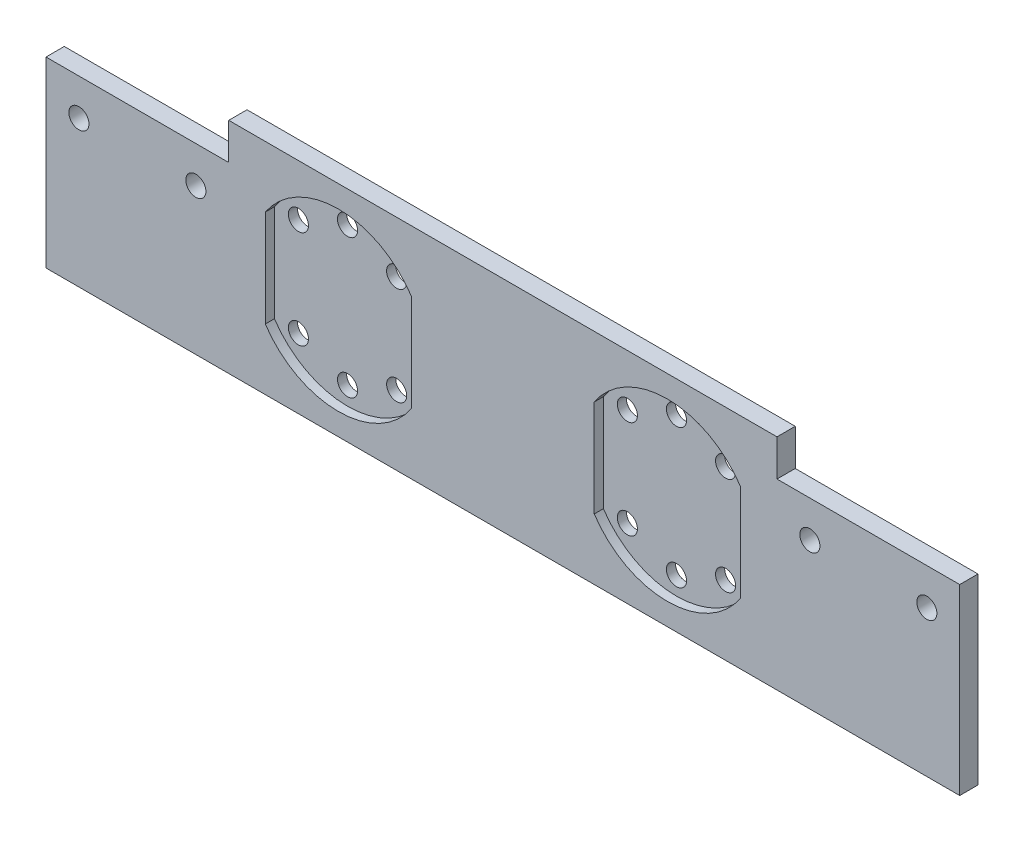
SolidWorks part; units mm, degrees
ref_plane "정면" through (0, 0, 0) normal (0, 0, 1) x (1, 0, 0)
ref_plane "윗면" through (0, 0, 0) normal (0, 1, 0) x (1, 0, 0)
ref_plane "우측면" through (0, 0, 0) normal (1, 0, 0) x (0, 0, -1)
sketch "스케치1" plane through (0, 0, 0) normal (0, 0, 1) x (1, 0, 0)
  line L1 (-145, 25) -> (145, 25)
  line L2 (-145, 25) -> (-145, -25)
  line L3 (-145, -25) -> (145, -25)
  line L4 (145, 25) -> (145, -25)
  line L5 (-145, 25) -> (145, -25) construction
  line L6 (-145, -25) -> (145, 25) construction
  point P0 (0, 0)
  dimension "D1" = 290
  dimension "D2" = 50
extrude "보스-돌출1" add sketch "스케치1" along normal blind 5
sketch "스케치3" plane through (0, 0, 5) normal (0, 0, 1) x (1, 0, 0)
  line L0 (-145, -25) -> (145, -25) construction
  line L1 (-145, 25) -> (-125, 25)
  line L2 (-145, 25) -> (-145, -25)
  line L3 (-145, -25) -> (-125, -25)
  line L4 (-125, 25) -> (-125, -25)
  dimension "D1" = 20
extrude "컷-돌출1" cut sketch "스케치3" against normal blind 10
mirror "대칭 복사1" about plane through (0, 0, 0) normal (1, 0, 0) of "컷-돌출1"
sketch "스케치4" plane through (0, 25, 0) normal (0, 1, 0) x (1, 0, 0)
  line L0 (125, 0) -> (-125, 0) construction
  line L1 (75, 0) -> (-75, 0)
  line L2 (75, 0) -> (75, -5)
  line L3 (75, -5) -> (-75, -5)
  line L4 (-75, 0) -> (-75, -5)
  line L5 (125, -5) -> (-125, -5) construction
  line L6 (-125, 0) -> (-125, -5) construction
  line L7 (125, 0) -> (125, -5) construction
  dimension "D1" = 50
  dimension "D2" = 50
extrude "보스-돌출2" add sketch "스케치4" along normal blind 10
sketch "스케치2" plane through (0, 0, 5) normal (0, 0, 1) x (1, 0, 0)
  line L0 (65, 18.26) -> (65, -8.27)
  line L1 (25, 18.263) -> (25, -8.273)
  line L2 (125, -25) -> (125, 25) construction
  line L3 (-125, -25) -> (125, -25) construction
  line L4 (9.7684, 4.995) -> (97.0125, 4.995) construction
  line L5 (44.999, 41.2348) -> (44.999, -42.4598) construction
  line L6 (0, -2.75) -> (0, 2.75) construction
  line L7 (-25, 18.263) -> (-25, -8.273)
  line L8 (-65, 18.26) -> (-65, -8.27)
  arc A0 (25, 18.263) -> (65, 18.26) centre (44.999, 4.995) cw
  arc A1 (25, -8.273) -> (65, -8.27) centre (44.999, 4.995) ccw
  circle A2 centre (58.44, -8.437) radius 2.75
  circle A3 centre (31.558, -8.437) radius 2.75
  circle A4 centre (44.999, -14) radius 2.75
  circle A5 centre (58.44, 18.427) radius 2.75
  circle A6 centre (44.999, 23.99) radius 2.75
  circle A7 centre (31.558, 18.427) radius 2.75
  circle A8 centre (-31.558, 18.427) radius 2.75
  circle A9 centre (-44.999, 23.99) radius 2.75
  circle A10 centre (-58.44, 18.427) radius 2.75
  circle A11 centre (-44.999, -14) radius 2.75
  circle A12 centre (-31.558, -8.437) radius 2.75
  circle A13 centre (-58.44, -8.437) radius 2.75
  arc A14 (-25, -8.273) -> (-65, -8.27) centre (-44.999, 4.995) cw
  arc A15 (-25, 18.263) -> (-65, 18.26) centre (-44.999, 4.995) ccw
  point P44 (0, 0)
  dimension "D4" = 24
  dimension "D5" = 24
  dimension "D7" = 5.5
  dimension "D11" = 5.5
  dimension "D1" = 60
  dimension "D2" = 100
  dimension "D3" = 26.53
  dimension "D6" = 16.73
  dimension "D8" = 16.563
  dimension "D9" = 6.56
  dimension "D10" = 11
extrude "컷-돌출2" cut sketch "스케치2" against normal blind 2.5
extrude "컷-돌출3" cut sketch "스케치2<2>" against normal through all contours A10 | A9 | A8 | A13 | A11 | A12 | A2 | A5 | A6 | A7 | A3 | A4 region at (58.44, -8.437, 5) region at (58.44, 18.427, 5) region at (44.999, 23.99, 5) region at (31.558, 18.427, 5) region at (-31.558, 18.427, 5) region at (-44.999, 23.99, 5) region at (-58.44, 18.427, 5) region at (-44.999, -14, 5) region at (-31.558, -8.437, 5) region at (-58.44, -8.437, 5)
sketch "스케치2<2>" plane through (0, 0, 5) normal (0, 0, 1) x (1, 0, 0) same geometry as "스케치2"
sketch "스케치5" plane through (0, 0, 5) normal (0, 0, 1) x (1, 0, 0)
  line L0 (-75, 25) -> (-125, 25) construction
  line L1 (-125, -25) -> (-125, 25) construction
  line L2 (0, -2.75) -> (0, 2.75) construction
  circle A0 centre (-84, 15) radius 2.75
  circle A1 centre (-116, 15) radius 2.75
  circle A2 centre (116, 15) radius 2.75
  circle A3 centre (84, 15) radius 2.75
  dimension "D3" = 5.5
  dimension "D4" = 5.5
  dimension "D5" = 9
  dimension "D1" = 10
  dimension "D2" = 10
  dimension "D6" = 41
extrude "컷-돌출4" cut sketch "스케치5" against normal through all
